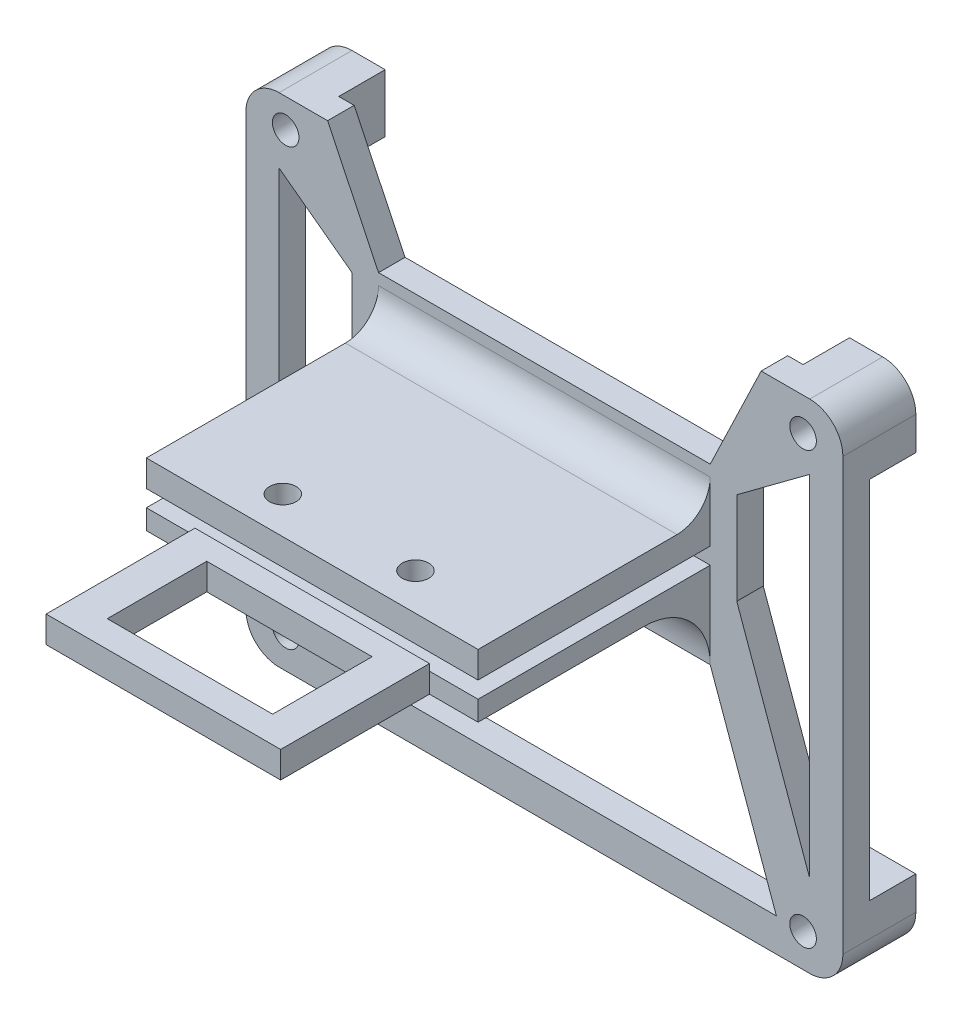
SolidWorks part; units mm, degrees
ref_plane "前视基准面" through (0, 0, 0) normal (0, 0, 1) x (1, 0, 0)
ref_plane "上视基准面" through (0, 0, 0) normal (0, 1, 0) x (1, 0, 0)
ref_plane "右视基准面" through (0, 0, 0) normal (1, 0, 0) x (0, 0, -1)
sketch "草图1" plane through (0, 0, 0) normal (0, 0, 1) x (1, 0, 0)
  line L5 (-39, -32.5) -> (39, 32.5) construction
  line L6 (-39, 32.5) -> (39, -32.5) construction
  line L7 (40, -37.5) -> (-40, -37.5)
  line L8 (45, -32.5) -> (45, 32.5)
  line L9 (40, 37.5) -> (-40, 37.5)
  line L10 (-45, -32.5) -> (-45, 32.5)
  line L11 (45, -37.5) -> (-45, 37.5) construction
  line L12 (45, 37.5) -> (-45, -37.5) construction
  circle A0 centre (-39, 33.1228) radius 2
  circle A1 centre (39, 32.5) radius 2
  circle A2 centre (-39, -32.5) radius 2
  circle A3 centre (39, -32.5) radius 2
  arc A4 (-40, -37.5) -> (-45, -32.5) centre (-40, -32.5) cw
  arc A5 (40, -37.5) -> (45, -32.5) centre (40, -32.5) ccw
  arc A6 (45, 32.5) -> (40, 37.5) centre (40, 32.5) ccw
  arc A7 (-40, 37.5) -> (-45, 32.5) centre (-40, 32.5) ccw
  point P0 (0, 0)
  point P11 (0, 0)
  dimension "D3" = 4
  dimension "D6" = 5
  dimension "D1" = 78
  dimension "D2" = 65
  dimension "D4" = 90
  dimension "D5" = 75
extrude "凸台-拉伸1" add sketch "草图1" along normal blind 4
sketch "草图2" plane through (0, 0, 0) normal (0, 0, -1) x (-1, 0, 0)
  line L0 (35, 41.0113) -> (35, -44.9821)
  line L1 (-33, 27.5) -> (-45, 27.5)
  line L2 (-33, 27.5) -> (-33, 37.5)
  line L3 (-33, 37.5) -> (-45, 37.5)
  line L4 (45, -32.5) -> (45, 32.5)
  line L5 (40, 37.5) -> (-40, 37.5)
  line L6 (-45, 32.5) -> (-45, -32.5)
  line L7 (-40, -37.5) -> (40, -37.5)
  line L8 (45, -32.5) -> (45, 32.5)
  line L9 (40, 37.5) -> (-40, 37.5)
  line L10 (-45, 32.5) -> (-45, -32.5)
  line L11 (-40, -37.5) -> (40, -37.5)
  line L12 (-45, 27.5) -> (-45, 37.5)
  line L13 (-33, 27.5) -> (-45, 37.5) construction
  line L14 (-33, 37.5) -> (-45, 27.5) construction
  line L15 (-33, -27.5) -> (-45, -27.5)
  line L16 (-33, -27.5) -> (-33, -37.5)
  line L17 (-33, -37.5) -> (-45, -37.5)
  line L18 (-45, -27.5) -> (-45, -37.5)
  line L19 (-33, -27.5) -> (-45, -37.5) construction
  line L20 (-33, -37.5) -> (-45, -27.5) construction
  line L21 (33, -27.5) -> (45, -27.5)
  line L22 (33, -27.5) -> (33, -37.5)
  line L23 (33, -37.5) -> (45, -37.5)
  line L24 (45, -27.5) -> (45, -37.5)
  line L25 (33, -27.5) -> (45, -37.5) construction
  line L26 (33, -37.5) -> (45, -27.5) construction
  line L27 (33, 28.7455) -> (45, 28.7455)
  line L28 (33, 28.7455) -> (33, 37.5)
  line L29 (33, 37.5) -> (45, 37.5)
  line L30 (45, 28.7455) -> (45, 37.5)
  line L31 (33, 28.7455) -> (45, 37.5) construction
  line L32 (33, 37.5) -> (45, 28.7455) construction
  line L33 (-35, 42.1281) -> (-35, -44.9821)
  arc A4 (40, -37.5) -> (45, -32.5) centre (40, -32.5) ccw
  arc A5 (45, 32.5) -> (40, 37.5) centre (40, 32.5) ccw
  arc A6 (-40, 37.5) -> (-45, 32.5) centre (-40, 32.5) ccw
  arc A7 (-45, -32.5) -> (-40, -37.5) centre (-40, -32.5) ccw
  arc A8 (40, -37.5) -> (45, -32.5) centre (40, -32.5) ccw
  arc A9 (45, 32.5) -> (40, 37.5) centre (40, 32.5) ccw
  arc A10 (-40, 37.5) -> (-45, 32.5) centre (-40, 32.5) ccw
  arc A11 (-45, -32.5) -> (-40, -37.5) centre (-40, -32.5) ccw
  point P0 (-39, 32.5)
  point P16 (-39, -32.5)
  point P24 (39, -32.5)
  point P30 (39, 33.1228)
  circle M15 centre (39, -32.5) radius 2
  circle M16 centre (39, 33.1228) radius 2
  arc M17 (40, -37.5) -> (45, -32.5) centre (40, -32.5) ccw
  line M18 (45, -32.5) -> (45, 32.5)
  arc M19 (45, 32.5) -> (40, 37.5) centre (40, 32.5) ccw
  line M20 (40, 37.5) -> (-40, 37.5)
  arc M21 (-40, 37.5) -> (-45, 32.5) centre (-40, 32.5) ccw
  line M22 (-45, 32.5) -> (-45, -32.5)
  arc M23 (-45, -32.5) -> (-40, -37.5) centre (-40, -32.5) ccw
  line M24 (-40, -37.5) -> (40, -37.5)
  circle M25 centre (-39, 32.5) radius 2
  circle M26 centre (-39, -32.5) radius 2
  dimension "D2" = 12
  dimension "D3" = 10
  dimension "D4" = 10
  dimension "D1" = 0
extrude "凸台-拉伸2" add sketch "草图2" along normal blind 7 contours L33 L9 L1 M21 M22 M25 | L33 L15 L10 M23 M24 M26 | L21 L0 M24 M17 M18 M15 | L0 L27 M18 M19 M20 M16 region at (-37.5, 37.3671, 0) region at (-40, -27.6414, 0) region at (35.1414, 32.5, 0) region at (35.1414, -32.5, 0)
sketch "草图3" plane through (0, 0, 4) normal (0, 0, 1) x (1, 0, 0)
  line L1 (-25, 14.8061) -> (25, 14.8061)
  line L2 (-25, 14.8061) -> (-25, 10.8061)
  line L3 (-25, 10.8061) -> (25, 10.8061)
  line L4 (25, 14.8061) -> (25, 10.8061)
  line L5 (-25, 14.8061) -> (25, 10.8061) construction
  line L6 (-25, 10.8061) -> (25, 14.8061) construction
  line L7 (-25, 8.3061) -> (25, 8.3061)
  line L8 (-25, 8.3061) -> (-25, 5.3061)
  line L9 (-25, 5.3061) -> (25, 5.3061)
  line L10 (25, 8.3061) -> (25, 5.3061)
  point P0 (0, 12.8061)
  dimension "D1" = 10.8061
  dimension "D2" = 4
  dimension "D3" = 50
  dimension "D4" = 0
  dimension "D5" = 3
  dimension "D6" = 50
  dimension "D7" = 2.5
extrude "凸台-拉伸3" add sketch "草图3" along normal blind 35
fillet "圆角1" radius 5 1 edges at (0, 14.8061, 4)
fillet "圆角2" radius 10 1 edges at (0, 5.3061, 4)
sketch "草图4" plane through (0, 14.8061, 0) normal (0, 1, 0) x (1, 0, 0)
  line L0 (26.75, -83.4337) -> (-26.75, -83.4337) construction
  circle A0 centre (25, -83.4337) radius 1.75 construction
  circle A1 centre (-25, -83.4337) radius 1.75 construction
  circle A2 centre (-10, -133.4337) radius 1.75 construction
  circle A3 centre (10, -133.4337) radius 1.75 construction
  circle A6 centre (-10, -33.4337) radius 2
  circle A7 centre (10, -33.4337) radius 2
  dimension "D1" = 4
  dimension "D2" = 4
extrude "切除-拉伸1" cut sketch "草图4" against normal through all
sketch "草图5" plane through (0, 5.3061, 0) normal (0, -1, 0) x (1, 0, 0)
  line L0 (-25, 39) -> (25, 39) construction
  line L1 (17.6777, 61.4337) -> (-17.6777, 61.4337)
  line L2 (17.6777, 61.4337) -> (17.6777, 39)
  line L3 (17.6777, 39) -> (-17.6777, 39)
  line L4 (-17.6777, 61.4337) -> (-17.6777, 39)
  line L6 (12.4646, 42.4337) -> (-12.4646, 42.4337)
  line L7 (12.4646, 42.4337) -> (12.4646, 57.4337)
  line L8 (12.4646, 57.4337) -> (-12.4646, 57.4337)
  line L9 (-12.4646, 42.4337) -> (-12.4646, 57.4337)
  line L10 (12.4646, 42.4337) -> (-12.4646, 57.4337) construction
  line L11 (12.4646, 57.4337) -> (-12.4646, 42.4337) construction
  point P7 (-8.4095, 54.9937)
  dimension "D1" = 15
  dimension "D2" = 4
extrude "凸台-拉伸4" add sketch "草图5" against normal blind 4
sketch "草图6" plane through (0, 0, 4) normal (0, 0, 1) x (1, 0, 0)
  line L0 (-25, -4.6939) -> (-34.9747, -32.5)
  line L1 (-34.9747, -32.5) -> (34.9747, -32.5)
  line L2 (0, -32.5) -> (0, -4.6939)
  line L3 (25, -4.6939) -> (-25, -4.6939) construction
  line L4 (25, -4.6939) -> (-25, -4.6939)
  line L5 (-40, -37.5) -> (40, -37.5) construction
  line L6 (25, -4.6939) -> (34.9747, -32.5)
  line L7 (-40, 19.5) -> (-40, -25.0762)
  line L8 (-40, -25.0762) -> (-29, 5.5879)
  line L9 (-29, 5.5879) -> (-29, 19.5)
  line L11 (25, 21.5) -> (-25, 21.5)
  line L12 (-25, 21.5) -> (-32.6821, 37.5)
  line L13 (-32.6821, 37.5) -> (32.6821, 37.5)
  line L15 (40, 37.5) -> (-40, 37.5) construction
  line L16 (-45, 32.5) -> (-45, -32.5) construction
  line L17 (-40, 19.5) -> (-40, 27.6614)
  line L18 (-40, 27.6614) -> (-29, 19.5)
  line L19 (40, -25.0762) -> (29, 5.5879)
  line L20 (40, 19.5) -> (40, -25.0762)
  line L21 (40, 19.5) -> (40, 27.6614)
  line L22 (40, 27.6614) -> (29, 19.5)
  line L23 (29, 5.5879) -> (29, 19.5)
  line L24 (25, 21.5) -> (32.6821, 37.5)
  line M33 (25, -4.6939) -> (-25, -4.6939)
  dimension "D1" = 5
  dimension "D2" = 0
  dimension "D3" = 16
  dimension "D4" = 5
  dimension "D5" = 16
extrude "切除-拉伸2" cut sketch "草图6" against normal blind 10 contours L23 L19 L20 L21 L22 | L18 L17 L7 L8 L9 | L11 L24 L13 L12 | L6 L2 L1 M33 | L1 L2 L0 M33 region at (-15.1319, -19.3677, 4) region at (15.1319, -19.3677, 4) region at (-35.568, 5.8259, 4) region at (0, 29.8551, 4) region at (35.568, 5.8259, 4)
sketch "草图7" plane through (0, 14.8061, 0) normal (0, 1, 0) x (1, 0, 0)
  line L0 (-10, -33.4337) -> (-10, 0)
  line L1 (-25, 0) -> (25, 0) construction
  line L3 (24.9229, -43.4337) -> (-44.9229, -43.4337)
  line L4 (24.9229, -43.4337) -> (24.9229, -23.4337)
  line L5 (24.9229, -23.4337) -> (-44.9229, -23.4337)
  line L6 (-44.9229, -43.4337) -> (-44.9229, -23.4337)
  line L7 (24.9229, -43.4337) -> (-44.9229, -23.4337) construction
  line L8 (24.9229, -23.4337) -> (-44.9229, -43.4337) construction
  line L9 (22, -55.4337) -> (-22, -55.4337)
  line L10 (22, -55.4337) -> (22, -11.4337)
  line L11 (22, -11.4337) -> (-22, -11.4337)
  line L12 (-22, -55.4337) -> (-22, -11.4337)
  line L13 (22, -55.4337) -> (-22, -11.4337) construction
  line L14 (22, -11.4337) -> (-22, -55.4337) construction
  point P9 (0, -33.4337)
  dimension "D1" = 20
  dimension "D2" = 44
  dimension "D3" = 44
  dimension "D4" = 10
